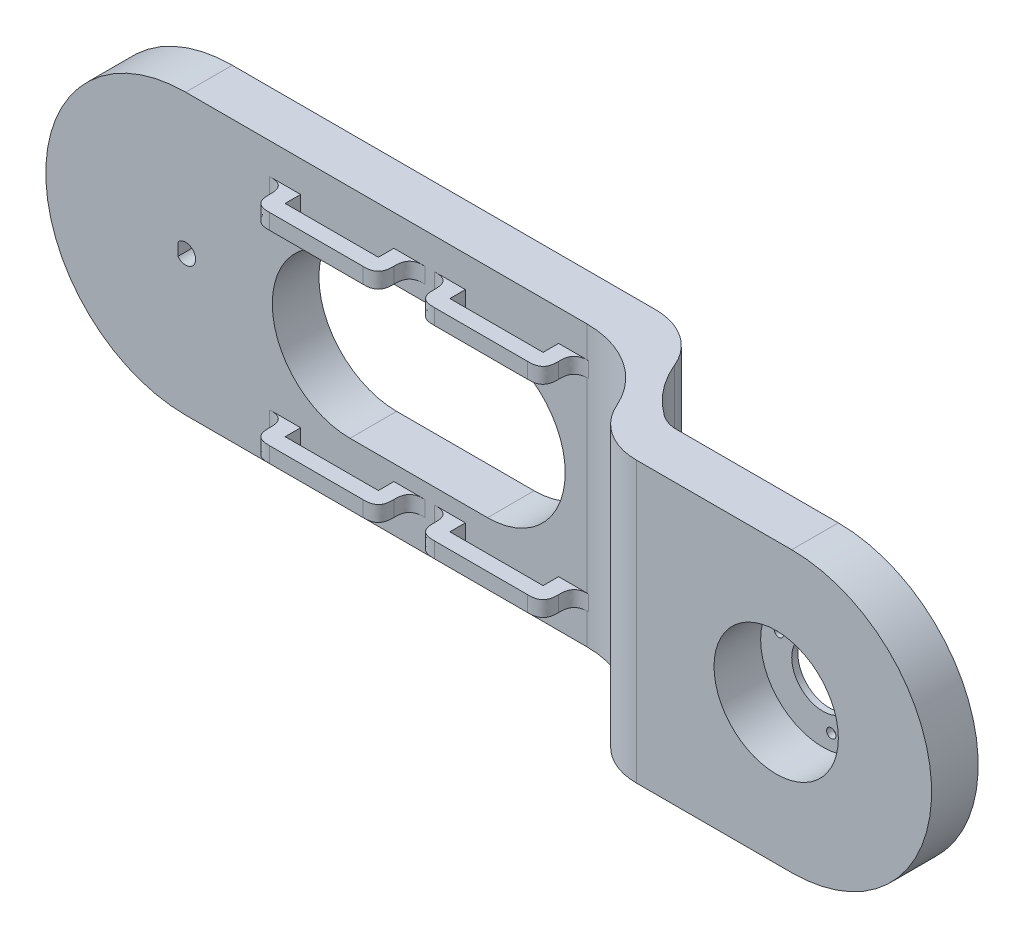
SolidWorks part; units mm, degrees
ref_plane "Plan de face" through (0, 0, 0) normal (0, 0, 1) x (1, 0, 0)
ref_plane "Plan de dessus" through (0, 0, 0) normal (0, 1, 0) x (1, 0, 0)
ref_plane "Plan de droite" through (0, 0, 0) normal (1, 0, 0) x (0, 0, -1)
sketch "Esquisse1" plane through (0, 0, 0) normal (0, 0, 1) x (1, 0, 0)
  line L0 (0, 90) -> (0, 0) construction
  line L1 (0, 90) -> (170, 90)
  line L3 (0, 0) -> (170, 0)
  line L4 (170, 90) -> (170, 0)
  arc A0 (0, 90) -> (0, 0) centre (0, 45) ccw
  dimension "D1" = 90
  dimension "D2" = 170
extrude "Boss.-Extru.1" add sketch "Esquisse1" along normal blind 15
sketch "Esquisse2" plane through (0, 0, 15) normal (0, 0, 1) x (1, 0, 0)
  line L0 (170, 0) -> (170, 90) construction
  line L1 (170, 90) -> (155, 90)
  line L2 (170, 90) -> (170, 0)
  line L3 (170, 0) -> (155, 0)
  line L4 (155, 90) -> (155, 0)
  line L5 (0, 0) -> (170, 0) construction
  line L6 (170, 90) -> (0, 90) construction
  point P8 (162.5, 90)
  dimension "D1" = 15
extrude "Boss.-Extru.2" add sketch "Esquisse2" along normal blind 15
sketch "Esquisse3" plane through (0, 0, 30) normal (0, 0, 1) x (1, 0, 0)
  line L0 (225, 90) -> (225, 0) construction
  line L1 (155, 90) -> (225, 90)
  line L2 (155, 90) -> (155, 0)
  line L3 (155, 0) -> (225, 0)
  line L5 (155, 0) -> (170, 0) construction
  arc A0 (225, 0) -> (225, 90) centre (225, 45) ccw
  point P12 (225, 90)
  dimension "D2" = 45
  dimension "D1" = 70
extrude "Boss.-Extru.3" add sketch "Esquisse3" along normal blind 15
sketch "Esquisse10" plane through (0, 0, 15) normal (0, 0, 1) x (1, 0, 0)
  line L0 (-2.498, 43) -> (-2.498, 47)
  arc A0 (-2.498, 43) -> (-2.498, 47) centre (0, 45) ccw
  dimension "D1" = 3.2
  dimension "D2" = 4
extrude "Enlèv. mat.-Extru.2" cut sketch "Esquisse10" against normal through all
sketch "Esquisse11" plane through (0, 0, 30) normal (0, 0, -1) x (-1, 0, 0)
  line L0 (-170, 0) -> (-170, 90) construction
  line L1 (-170, 0) -> (-225, 0) construction
  circle A0 centre (-220, 45) radius 20
  dimension "D1" = 50
  dimension "D2" = 45
extrude "Enlèv. mat.-Extru.3" cut sketch "Esquisse11" against normal blind 20
ref_plane "Plan1" through (0, 10, 0) normal (0, 1, 0) x (1, 0, 0)
ref_plane "Plan2" through (170, 45, 0) normal (0, -1, 0) x (-1, 0, 0)
sketch "Esquisse20" plane through (0, 10, 0) normal (0, 1, 0) x (1, 0, 0)
  line L0 (125, -25) -> (125, -15)
  line L1 (0, -15) -> (155, -15) construction
  line L2 (125, -15) -> (120, -15)
  line L3 (120, -15) -> (120, -20)
  line L4 (120, -20) -> (90, -20)
  line L5 (90, -20) -> (90, -15)
  line L6 (90, -15) -> (85, -15)
  line L7 (85, -15) -> (85, -25)
  line L8 (85, -25) -> (125, -25)
  line L9 (155, -45) -> (155, -15) construction
  dimension "D1" = 5
  dimension "D2" = 30
  dimension "D3" = 5
  dimension "D4" = 10
  dimension "D5" = 5
  dimension "D6" = 30
extrude "Boss.-Extru.5" add sketch "Esquisse20" along normal blind 5
mirror "Symétrie2" about plane through (170, 45, 0) normal (0, -1, 0) of "Boss.-Extru.5"
pattern_linear "Répétition linéaire2" count 2 spacing 53 along (-1, 0, 0) of "Symétrie2"
fillet "Congé3" radius 5 16 edges at (125, 77.5, 15) (125, 77.5, 25) (85, 77.5, 15) (85, 77.5, 25) (32, 77.5, 15) (32, 77.5, 25) (72, 77.5, 15) (72, 77.5, 25) (32, 12.5, 15) (32, 12.5, 25) (72, 12.5, 15) (72, 12.5, 25) (85, 12.5, 15) (125, 12.5, 15) (85, 12.5, 25) (125, 12.5, 25) curvature continuous yes
fillet "Congé4" radius 20 1 edges at (155, 45, 45)
fillet "Congé8" radius 30 2 edges at (155, 45, 15) (170, 45, 0)
sketch "Esquisse21" plane through (0, 90, 0) normal (0, 1, 0) x (1, 0, 0)
  arc A0 (170, -30) -> (152.1547, -2.5726) centre (188.6086, 1.6266) cw
  arc A1 (170, -30) -> (140, 0) centre (140, -30) ccw construction
  arc A2 (152.1547, -2.5726) -> (170, -30) centre (140, -30) cw
extrude "Enlèv. mat.-Extru.4" cut sketch "Esquisse21" against normal through all
fillet "Congé9" radius 20 1 edges at (152.1547, 45, 2.5726)
fillet "Congé10" radius 10 1 edges at (170, 45, 30)
sketch "Esquisse23" plane through (0, 0, 30) normal (0, 0, -1) x (-1, 0, 0)
  circle A1 centre (-220, 45) radius 20
  dimension "D1" = 40
extrude "Boss.-Extru.7" add sketch "Esquisse23" along normal blind 2 separate body
sketch "Esquisse24" plane through (0, 0, 28) normal (0, 0, -1) x (-1, 0, 0)
  circle A0 centre (-220, 45) radius 10
  circle A1 centre (-205.8632, 50.015) radius 1.5
  circle A2 centre (-222.7253, 30.2497) radius 1.5
  circle A3 centre (-231.4115, 54.7354) radius 1.5
  dimension "D1" = 20
extrude "Enlèv. mat.-Extru.5" cut sketch "Esquisse24" against normal blind 5
sketch "Esquisse25" plane through (0, 0, 15) normal (0, 0, 1) x (1, 0, 0)
  line L0 (52.8768, 45) -> (97.1232, 45) construction
  line L1 (52.8768, 70) -> (97.1232, 70)
  line L2 (52.8768, 20) -> (97.1232, 20)
  arc A0 (52.8768, 70) -> (52.8768, 20) centre (52.8768, 45) ccw
  arc A1 (97.1232, 20) -> (97.1232, 70) centre (97.1232, 45) ccw
  point P2 (75, 45)
  point P7 (0, 0)
  point P9 (0, 0)
  dimension "D4" = 44.2465
  dimension "D1" = 25
  dimension "D2" = 75
  dimension "D3" = 25
extrude "Enlèv. mat.-Extru.6" cut sketch "Esquisse25" against normal through all
